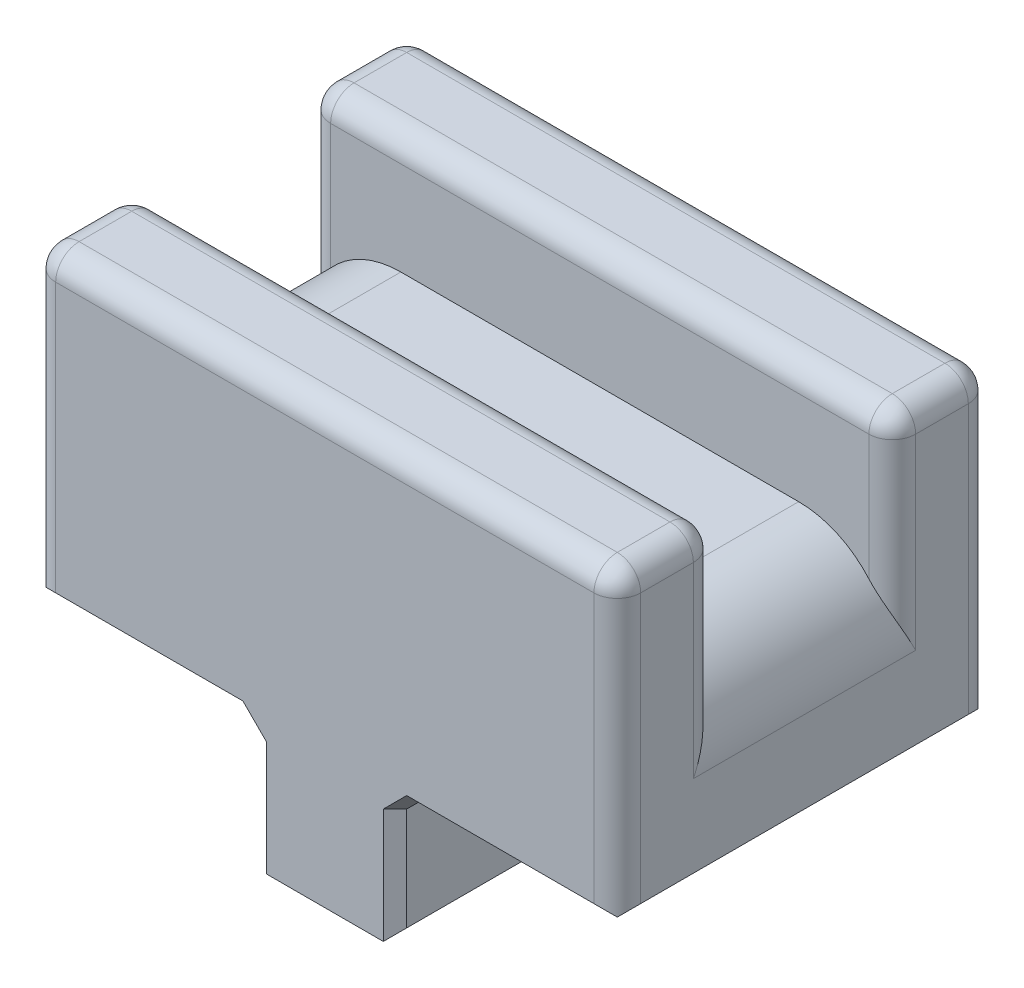
SolidWorks part; units mm, degrees
material "PA Typ 6"
ref_plane "Ebene vorne" through (0, 0, 0) normal (0, 0, 1) x (1, 0, 0)
ref_plane "Ebene oben" through (0, 0, 0) normal (0, 1, 0) x (1, 0, 0)
ref_plane "Ebene rechts" through (0, 0, 0) normal (1, 0, 0) x (0, 0, -1)
sketch "Skizze1" plane through (0, 0, 0) normal (0, 1, 0) x (1, 0, 0)
  line L1 (-12.5, -8) -> (12.5, -8)
  line L2 (-12.5, -8) -> (-12.5, 8)
  line L3 (-12.5, 8) -> (12.5, 8)
  line L4 (12.5, -8) -> (12.5, 8)
  line L5 (-12.5, -8) -> (12.5, 8) construction
  line L6 (-12.5, 8) -> (12.5, -8) construction
  point P0 (0, 0)
  dimension "D1" = 25
  dimension "D2" = 16
extrude "Aufsatz-Linear austragen1" add sketch "Skizze1" along normal blind 13
sketch "Skizze2" plane through (0, 13, 0) normal (0, 1, 0) x (1, 0, 0)
  line L0 (12.5, -8) -> (12.5, 8) construction
  line L1 (-12.5, 3.75) -> (12.5, 3.75)
  line L2 (-12.5, 3.75) -> (-12.5, -3.75)
  line L3 (-12.5, -3.75) -> (12.5, -3.75)
  line L4 (12.5, 3.75) -> (12.5, -3.75)
  line L5 (-12.5, 3.75) -> (12.5, -3.75) construction
  line L6 (-12.5, -3.75) -> (12.5, 3.75) construction
  point P0 (0, 0)
  dimension "D1" = 7.5
extrude "Schnitt-Linear austragen1" cut sketch "Skizze2" against normal blind 5
sketch "Skizze3" plane through (0, 0, 0) normal (0, -1, 0) x (1, 0, 0)
  line L5 (-3, -8) -> (3, -8)
  line L6 (-3, -8) -> (-3, 8)
  line L7 (-3, 8) -> (3, 8)
  line L8 (3, -8) -> (3, 8)
  line L9 (-3, -8) -> (3, 8) construction
  line L10 (-3, 8) -> (3, -8) construction
  point P0 (0, 0)
  dimension "D1" = 16
  dimension "D2" = 6
extrude "Aufsatz-Linear austragen2" add sketch "Skizze3" along normal blind 5.4
fillet "Verrundung1" radius 1 6 edges at (0, 13, 3.75) (12.5, 10.5, -3.75) (-12.5, 10.5, -3.75) (-12.5, 10.5, 3.75) (12.5, 10.5, 3.75) (0, 13, -3.75)
chamfer "Fase1" distance 0.5 angle 45 14 edges at (7.75, 0, 8) (12.5, 0, 0) (7.75, 0, -8) (3, -2.7, -8) (3, -5.4, 0) (3, -2.7, 8) (3, 0, 0) (-7.75, 0, -8) (-12.5, 0, 0) (-7.75, 0, 8) (-3, 0, 0) (-3, -2.7, 8) (-3, -5.4, 0) (-3, -2.7, -8)
fillet "Verrundung2" radius 4 2 edges at (12.5, 8, 0) (-12.5, 8, 0)
fillet "Verrundung3" radius 1 14 edges at (-12.5, 6.75, 8) (0, 13, 8) (12.5, 6.75, 8) (12.5, 6.75, -8) (-12.5, 6.75, -8) (0, 13, -8) (-12.2071, 12.7071, -4.0429) (-12.2071, 12.7071, 4.0429) (12.2071, 12.7071, -4.0429) (12.2071, 12.7071, 4.0429) (-12.5, 13, -6.375) (-12.5, 13, 6.375) (12.5, 13, -6.375) (12.5, 13, 6.375)
